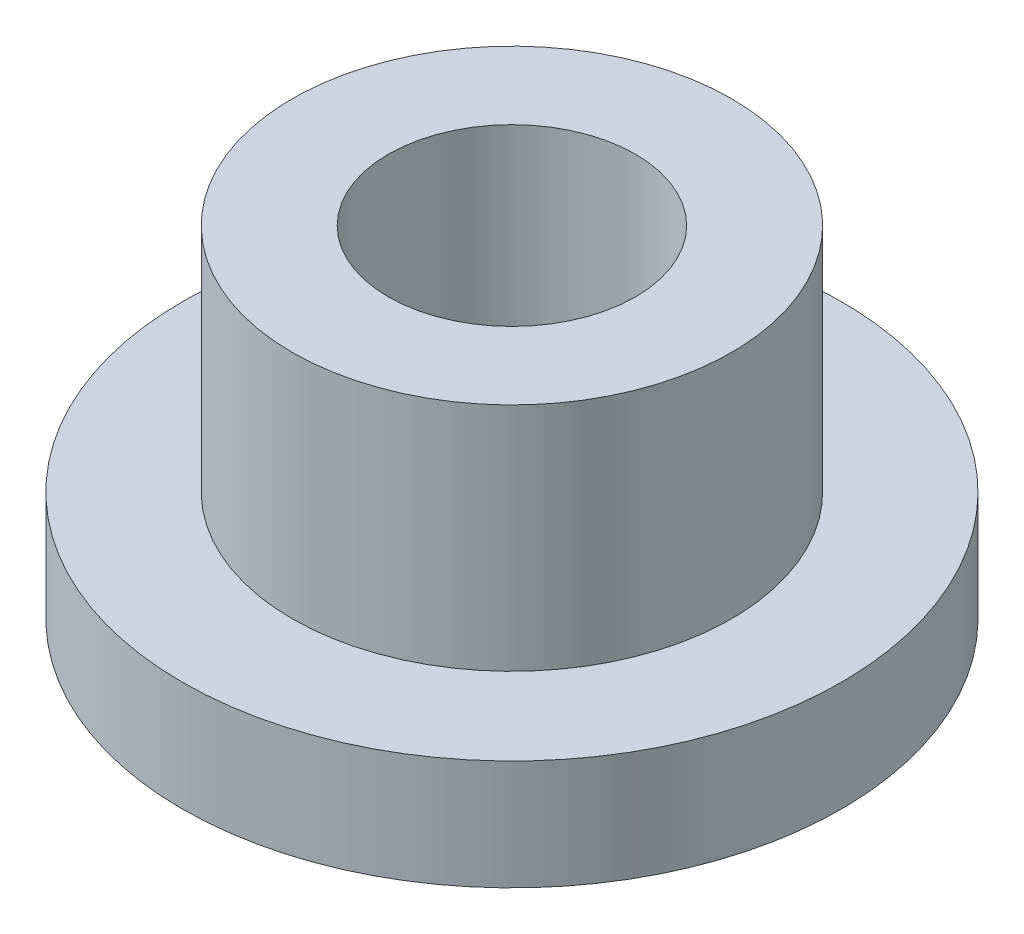
SolidWorks part; units mm, degrees
ref_plane "Front Plane" through (0, 0, 0) normal (0, 0, 1) x (1, 0, 0)
ref_plane "Top Plane" through (0, 0, 0) normal (0, 1, 0) x (1, 0, 0)
ref_plane "Right Plane" through (0, 0, 0) normal (1, 0, 0) x (0, 0, -1)
sketch "Sketch1" plane through (0, 0, 0) normal (0, 1, 0) x (1, 0, 0)
  line L1 (0.8949, -1.55) -> (1.7898, 0)
  line L2 (1.7898, 0) -> (0.8949, 1.55)
  line L3 (0.8949, 1.55) -> (-0.8949, 1.55)
  line L4 (-0.8949, 1.55) -> (-1.7898, 0)
  line L5 (-1.7898, 0) -> (-0.8949, -1.55)
  line L6 (-0.8949, -1.55) -> (0.8949, -1.55)
  circle A0 centre (0, 0) radius 2
  circle A1 centre (0, 0) radius 1.125
  circle A2 centre (0, 0) radius 1.55 construction
  circle A3 centre (0, 0) radius 3
  point P4 (0, 1.55)
  dimension "D1" = 4
  dimension "D2" = 2.25
  dimension "D4" = 6
  dimension "D3" = 3.1
extrude "Boss-Extrude1" add sketch "Sketch1" along normal blind 2.1 contours A0
extrude "Boss-Extrude2" add sketch "Sketch1<3>" against normal blind 1 contours A3 | L3 L4 L5 L6 L1 L2
sketch "Sketch1<3>" plane through (0, 0, 0) normal (0, 1, 0) x (1, 0, 0) same geometry as "Sketch1"
extrude "Cut-Extrude1" cut sketch "Sketch1<4>" along normal through all both and the other way through all contours A1
sketch "Sketch1<4>" plane through (0, 0, 0) normal (0, 1, 0) x (1, 0, 0) same geometry as "Sketch1"
